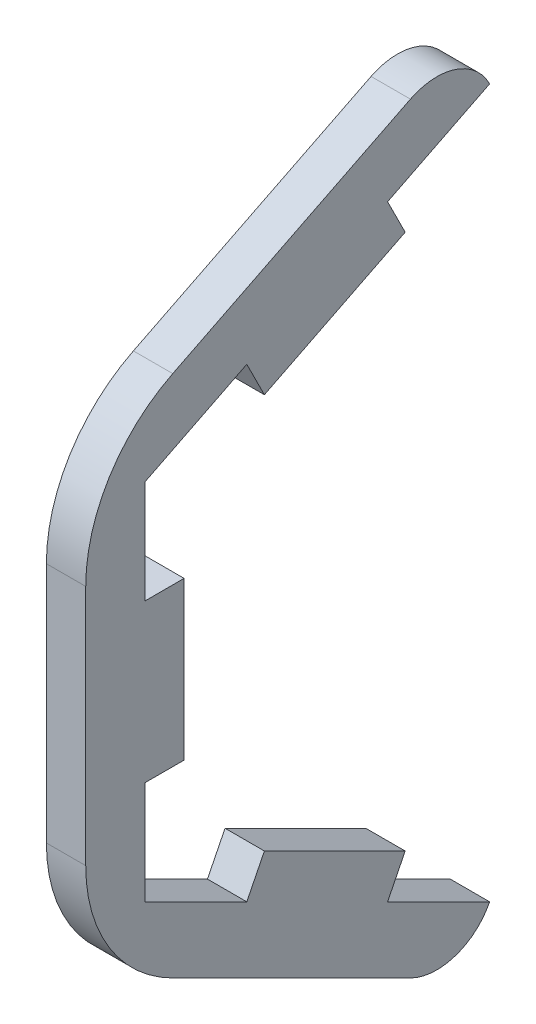
SolidWorks part; units mm, degrees
material "Plain Carbon Steel"
ref_plane "Front Plane" through (0, 0, 0) normal (0, 0, 1) x (1, 0, 0)
ref_plane "Top Plane" through (0, 0, 0) normal (0, 1, 0) x (1, 0, 0)
ref_plane "Right Plane" through (0, 0, 0) normal (1, 0, 0) x (0, 0, -1)
sketch "Sketch1" plane through (0, 0, 0) normal (1, 0, 0) x (0, 0, -1)
  line L0 (-160.655, 50.8) -> (93.345, 50.8)
  line L1 (93.345, 50.8) -> (93.345, -50.8)
  line L2 (93.345, -50.8) -> (-160.655, -50.8)
  line L3 (93.345, 0) -> (55.245, 50.8)
  line L4 (93.345, 0) -> (55.245, -50.8)
  circle A0 centre (0, 0) radius 38.1
  circle A1 centre (0, 0) radius 7.9375
  circle A2 centre (-38.1, 0) radius 7.9375
  circle A3 centre (-88.9, 0) radius 7.9375
  circle A4 centre (-88.9, 0) radius 39.751
  circle A5 centre (-38.1, 0) radius 25.4
  circle A6 centre (-160.655, 0) radius 11.1125
  circle A7 centre (-88.9, 0) radius 23.368
  circle A8 centre (-160.655, 0) radius 33.655
  circle A9 centre (-160.655, 0) radius 76.2
  circle A10 centre (-160.655, 0) radius 50.8
  dimension "D1" = 38.1
  dimension "D3" = 71.755
  dimension "D4" = 15.875
  dimension "D5" = 101.6
  dimension "D9" = 50.8
  dimension "D10" = 67.31
  dimension "D11" = 79.502
  dimension "D12" = 46.736
  dimension "D2" = 50.8
  dimension "D6" = 254
  dimension "D7" = 38.1
  dimension "D8" = 38.1
extrude "Boss-Extrude1" add sketch "Sketch1" along normal blind 12.7 contours A5 A0 A1 | A0 A5 | A10 A7 A9 A3 | A10 A7 A9 A4 | A7 A10 A4 | A7 A10 | A10 A4 A9 A7 | A9 A4 A5 A7 | A10 L2 A9 A4 | A4 A10 A8 | A8 A6 | A10 A4 A9 L0 | A9 A4 A5 A0 L2 L4 L3 L0 | A9 A3 A7 | A4 A5 | A0 A5 A4 A2 | A4 A8
hole_wizard "#8 Clearance Hole1" positions "Sketch3" profile "Sketch4" hole size "#8" standard "ANSI Inch" end condition through all
sketch "Sketch3" plane through (0, 0, 0) normal (-1, 0, 0) x (0, 0, 1)
  point P0 (-17.6911, 17.6911)
  point P3 (17.6911, 17.6911)
  point P6 (17.6911, -17.6911)
  point P9 (-17.6911, -17.6911)
sketch "Sketch4" plane through (0, 17.6911, -17.6911) normal (0, 1, 0) x (0, 0, 1)
  line L0 (0, 0) -> (0, 12.7)
  line L1 (0, 12.7) -> (2.2479, 12.7)
  line L2 (2.2479, 12.7) -> (2.2479, 0)
  line L5 (2.2479, 0) -> (0, 0)
  line L11 (0, -6.35) -> (0, 107.95) construction
  dimension "Thru Hole Dia." = 4.4958
  dimension "Thru Hole Depth" = 12.7
sketch "Sketch5" plane through (0, 0, 0) normal (-1, 0, 0) x (0, 0, 1)
  circle A0 centre (0, 0) radius 18.415
extrude "Cut-Extrude1" cut sketch "Sketch5" against normal through all
sketch "Sketch7" plane through (0, 0, 0) normal (-1, 0, 0) x (0, 0, 1)
  circle A0 centre (-55.245, 0) radius 9.525
  dimension "D1" = 38.1
extrude "Cut-Extrude2" cut sketch "Sketch7" against normal through all
sketch "Sketch8" plane through (12.7, 0, 0) normal (1, 0, 0) x (0, 0, -1)
  line L0 (-160.655, 50.8) -> (-211.455, 25.4)
  line L1 (-211.455, 25.4) -> (-211.455, -25.4)
  line L2 (-211.455, -25.4) -> (-160.655, -50.8)
  line L3 (-160.655, -50.8) -> (-233.2397, -50.8)
  line L4 (-233.2397, -50.8) -> (-233.2397, 50.8)
  line L5 (-233.2397, 50.8) -> (-160.655, 50.8)
  line L6 (-211.455, 0) -> (-160.655, 0) construction
  arc A0 (-160.655, 50.8) -> (-160.655, -50.8) centre (-160.655, 0) ccw construction
  dimension "D1" = 50.8
extrude "Cut-Extrude3" cut sketch "Sketch8" against normal through all
sketch "Sketch9" plane through (12.7, 0, 0) normal (1, 0, 0) x (0, 0, -1)
  line L0 (-160.655, 50.8) -> (-211.455, 25.4)
  line L1 (-211.455, 25.4) -> (-211.455, 0)
  line L2 (-211.455, 0) -> (-211.455, -25.4)
  line L3 (-211.455, -25.4) -> (-160.655, -50.8)
  line L4 (-160.655, -50.8) -> (-160.655, -40.64)
  line L5 (-160.655, -40.64) -> (-202.7493, 0)
  line L6 (-202.7493, 0) -> (-160.655, 40.64)
  line L7 (-160.655, 40.64) -> (-160.655, 50.8)
  line L8 (-160.655, -50.8) -> (-201.295, -30.48) construction
  line L9 (-201.295, 30.48) -> (-160.655, 50.8) construction
  arc A0 (-201.295, 30.48) -> (-201.295, -30.48) centre (-160.655, 0) ccw construction
extrude "Boss-Extrude2" add sketch "Sketch9" against normal blind 12.7
sketch "Sketch10" plane through (0, 0, 0) normal (-1, 0, 0) x (0, 0, 1)
  line L0 (-79.0575, -19.05) -> (-79.0575, 19.05)
  line L1 (-93.345, 0) -> (-55.245, -50.8) construction
  line L3 (-93.345, 0) -> (-55.245, 50.8) construction
  line L4 (-79.0575, 19.05) -> (-93.345, 0)
  line L5 (-93.345, 0) -> (-79.0575, -19.05)
extrude "Cut-Extrude4" cut sketch "Sketch10" against normal through all
sketch "Sketch11" plane through (0, 50.8, 0) normal (0, 1, 0) x (1, 0, 0)
  line L0 (0, -160.655) -> (0, 55.245) construction
  line L1 (0, 36.322) -> (12.7, 36.322)
  line L2 (0, 36.322) -> (0, -141.732)
  line L3 (0, -141.732) -> (12.7, -141.732)
  line L4 (12.7, 36.322) -> (12.7, -141.732)
  line L5 (12.7, -160.655) -> (12.7, 55.245) construction
  line L6 (12.7, -141.605) -> (0, -141.605) construction
  line L7 (0, 36.195) -> (12.7, 36.195) construction
  dimension "D1" = 0.127
  dimension "D2" = 0.127
extrude "Cut-Extrude5" cut sketch "Sketch11" against normal blind 3.175
mirror "Mirror1" about plane through (0, 0, 0) normal (0, 1, 0) of "Cut-Extrude5"
sketch "Sketch12" plane through (12.7, 0, 0) normal (1, 0, 0) x (0, 0, -1)
  line L16 (-162.154, 57.15) -> (-166.9165, 66.675)
  line L17 (-166.9165, 66.675) -> (-185.9665, 66.675)
  line L18 (-185.9665, 66.675) -> (-243.205, 43.9892)
  line L19 (-243.205, 43.9892) -> (-243.205, -43.9892)
  line L20 (-243.205, -43.9892) -> (-185.9665, -66.675)
  line L21 (-185.9665, -66.675) -> (-166.9165, -66.675)
  line L22 (-166.9165, -66.675) -> (-162.154, -57.15)
  line L23 (-243.205, 43.9892) -> (-217.805, 29.3245) construction
  line L24 (-217.805, -29.3245) -> (-243.205, -43.9892) construction
  line L32 (-162.154, -57.15) -> (-135.382, -57.15)
  line L33 (-135.382, -57.15) -> (-135.382, -53.975)
  line L34 (-135.382, -53.975) -> (29.972, -53.975)
  line L35 (29.972, -53.975) -> (29.972, -57.15)
  line L36 (29.972, -57.15) -> (58.42, -57.15)
  line L37 (58.42, -57.15) -> (85.4075, -21.1667)
  line L38 (85.4075, -21.1667) -> (85.4075, 21.1667)
  line L39 (85.4075, 21.1667) -> (58.42, 57.15)
  line L40 (58.42, 57.15) -> (29.972, 57.15)
  line L41 (29.972, 57.15) -> (29.972, 53.975)
  line L42 (29.972, 53.975) -> (-135.382, 53.975)
  line L43 (-135.382, 53.975) -> (-135.382, 57.15)
  line L44 (-135.382, 57.15) -> (-162.154, 57.15)
  line L45 (-162.154, 57.15) -> (-217.805, 29.3245)
  line L46 (-217.805, 29.3245) -> (-217.805, -29.3245)
  line L47 (-217.805, -29.3245) -> (-162.154, -57.15)
  line L48 (-162.154, -57.15) -> (-135.382, -57.15)
  line L49 (-135.382, -57.15) -> (-135.382, -53.975)
  line L50 (-135.382, -53.975) -> (29.972, -53.975)
  line L51 (29.972, -53.975) -> (29.972, -57.15)
  line L52 (29.972, -57.15) -> (58.42, -57.15)
  line L53 (58.42, -57.15) -> (85.4075, -21.1667)
  line L54 (85.4075, -21.1667) -> (85.4075, 21.1667)
  line L55 (85.4075, 21.1667) -> (58.42, 57.15)
  line L56 (58.42, 57.15) -> (29.972, 57.15)
  line L57 (29.972, 57.15) -> (29.972, 53.975)
  line L58 (29.972, 53.975) -> (-135.382, 53.975)
  line L59 (-135.382, 53.975) -> (-135.382, 57.15)
  line L60 (-135.382, 57.15) -> (-162.154, 57.15)
  line L61 (-162.154, 57.15) -> (-217.805, 29.3245)
  line L62 (-217.805, 29.3245) -> (-217.805, -29.3245)
  line L63 (-217.805, -29.3245) -> (-162.154, -57.15)
  circle A0 centre (-160.655, 0) radius 76.2
  dimension "D2" = 9.525
  dimension "D3" = 9.525
  dimension "D4" = 25.4
  dimension "D5" = 120
  dimension "D6" = 120
  dimension "D7" = 19.05
  dimension "D8" = 19.05
  dimension "D1" = 6.35
extrude "Boss-Extrude3" add sketch "Sketch12" against normal blind 6.35 separate body contours A0 L18 L19 L20 | L18 A0 L20 L21 L22 L63 L62 L61 L16 L17
sketch "Sketch13" plane through (12.7, 0, 0) normal (1, 0, 0) x (0, 0, -1)
  line L32 (-161.2546, -53.34) -> (-139.192, -53.34)
  line L33 (-139.192, -53.34) -> (-139.192, -50.165)
  line L34 (-139.192, -50.165) -> (33.782, -50.165)
  line L35 (33.782, -50.165) -> (33.782, -53.34)
  line L36 (33.782, -53.34) -> (56.515, -53.34)
  line L37 (56.515, -53.34) -> (81.5975, -19.8967)
  line L38 (81.5975, -19.8967) -> (81.5975, 19.8967)
  line L39 (81.5975, 19.8967) -> (56.515, 53.34)
  line L40 (56.515, 53.34) -> (33.782, 53.34)
  line L41 (33.782, 53.34) -> (33.782, 50.165)
  line L42 (33.782, 50.165) -> (-139.192, 50.165)
  line L43 (-139.192, 50.165) -> (-139.192, 53.34)
  line L44 (-139.192, 53.34) -> (-161.2546, 53.34)
  line L45 (-161.2546, 53.34) -> (-213.995, 26.9698)
  line L46 (-213.995, 26.9698) -> (-213.995, -26.9698)
  line L47 (-213.995, -26.9698) -> (-161.2546, -53.34)
  line L48 (-161.2546, -53.34) -> (-139.192, -53.34)
  line L49 (-139.192, -53.34) -> (-139.192, -50.165)
  line L50 (-139.192, -50.165) -> (33.782, -50.165)
  line L51 (33.782, -50.165) -> (33.782, -53.34)
  line L52 (33.782, -53.34) -> (56.515, -53.34)
  line L53 (56.515, -53.34) -> (81.5975, -19.8967)
  line L54 (81.5975, -19.8967) -> (81.5975, 19.8967)
  line L55 (81.5975, 19.8967) -> (56.515, 53.34)
  line L56 (56.515, 53.34) -> (33.782, 53.34)
  line L57 (33.782, 53.34) -> (33.782, 50.165)
  line L58 (33.782, 50.165) -> (-139.192, 50.165)
  line L59 (-139.192, 50.165) -> (-139.192, 53.34)
  line L60 (-139.192, 53.34) -> (-161.2546, 53.34)
  line L61 (-161.2546, 53.34) -> (-213.995, 26.9698)
  line L62 (-213.995, 26.9698) -> (-213.995, -26.9698)
  line L63 (-213.995, -26.9698) -> (-161.2546, -53.34)
  dimension "D1" = 2.54
extrude "Cut-Extrude6" cut sketch "Sketch13" against normal through all
hole_wizard "3/8 Clearance Hole1" [suppressed] positions "Sketch15" profile "Sketch14" hole size "3/8" standard "ANSI Inch"
sketch "Sketch15" plane through (12.7, 0, 0) normal (1, 0, 0) x (0, 0, -1)
  line L0 (-185.9665, -66.675) -> (-177.394, -49.53) construction
  line L1 (-217.805, -29.3245) -> (-162.154, -57.15) construction
  line L3 (-230.505, 49.0227) -> (-230.505, -49.0227) construction
  line L4 (-185.9665, 66.675) -> (-243.205, 43.9892) construction
  line L5 (-243.205, -43.9892) -> (-185.9665, -66.675) construction
  line L11 (-243.205, 0) -> (-230.505, 0) construction
  line L12 (-243.205, 43.9892) -> (-243.205, -43.9892) construction
  line L13 (-230.505, 0) -> (-217.805, 0) construction
  line L14 (-217.805, 29.3245) -> (-217.805, -29.3245) construction
  line L16 (-181.6803, -58.1025) -> (-230.505, -33.6901) construction
  line L18 (-185.9665, 66.675) -> (-177.394, 49.53) construction
  line L19 (-162.154, 57.15) -> (-217.805, 29.3245) construction
  line L23 (-230.505, 33.6901) -> (-181.6803, 58.1025) construction
  point P0 (-230.505, 0)
  point P2 (-230.505, 33.6901)
  point P4 (-202.1069, 47.8892)
  point P6 (-230.505, -33.6901)
  point P8 (-202.1069, -47.8892)
  dimension "D1" = 31.75
sketch "Sketch14" plane through (12.7, 0, 230.505) normal (0, 1, 0) x (0, 0, -1)
  line L0 (0, 0) -> (0, 15.7295)
  line L1 (0, 15.7295) -> (5.0419, 12.7)
  line L2 (5.0419, 12.7) -> (5.0419, 0)
  line L5 (5.0419, 0) -> (0, 0)
  line L10 (0, 15.7295) -> (-5.0419, 12.7) construction
  line L11 (0, -6.35) -> (0, 107.95) construction
  dimension "Hole Dia." = 10.0838
  dimension "Hole Depth" = 12.7
  dimension "Drill Angle" = 118
fillet "Fillet1" radius 12.7 6 edges at (9.525, 43.9892, 243.205) (9.525, -43.9892, 243.205) (9.525, -66.675, 166.9165) (9.525, -66.675, 185.9665) (9.525, 66.675, 166.9165) (9.525, 66.675, 185.9665)
sketch "Sketch16" plane through (12.7, 0, 0) normal (1, 0, 0) x (0, 0, -1)
  line L0 (-217.805, 29.3245) -> (-217.805, -29.3245) construction
  line L1 (-217.805, 12.7) -> (-211.455, 12.7)
  line L2 (-217.805, 12.7) -> (-217.805, -12.7)
  line L3 (-217.805, -12.7) -> (-211.455, -12.7)
  line L4 (-211.455, 12.7) -> (-211.455, -12.7)
  line L5 (-178.6203, -48.9169) -> (-175.7805, -43.2373)
  line L6 (-217.805, -29.3245) -> (-162.154, -57.15) construction
  line L7 (-175.7805, -43.2373) -> (-198.4989, -31.878)
  line L8 (-198.4989, -31.878) -> (-201.3387, -37.5576)
  line L9 (-201.3387, -37.5576) -> (-178.6203, -48.9169)
  line L10 (-201.3387, 37.5576) -> (-198.4989, 31.878)
  line L11 (-162.154, 57.15) -> (-217.805, 29.3245) construction
  line L12 (-198.4989, 31.878) -> (-175.7805, 43.2373)
  line L13 (-175.7805, 43.2373) -> (-178.6203, 48.9169)
  line L14 (-178.6203, 48.9169) -> (-201.3387, 37.5576)
  point P16 (-189.9795, 43.2373)
  point P19 (-189.9795, -43.2373)
  point P20 (-217.805, 0)
  dimension "D1" = 6.35
  dimension "D2" = 25.4
extrude "Boss-Extrude4" add sketch "Sketch16" against normal up to surface (6.35 mm away) up to face at (6.35, 0, 196.1429)
sketch "Sketch17" plane through (12.7, 0, 0) normal (1, 0, 0) x (0, 0, -1)
  line L22 (-174.7656, 66.675) -> (-183.5415, 66.675) construction
  line L23 (-188.2209, 65.7815) -> (-235.1844, 47.1681) construction
  line L24 (-243.205, 35.3616) -> (-243.205, -35.3616) construction
  line L25 (-235.1844, -47.1681) -> (-188.2209, -65.7815) construction
  line L26 (-183.5415, -66.675) -> (-174.7656, -66.675) construction
  line L27 (-174.7656, 66.675) -> (-183.5415, 66.675)
  line L28 (-188.2209, 65.7815) -> (-235.1844, 47.1681)
  line L29 (-243.205, 35.3616) -> (-243.205, -35.3616)
  line L30 (-235.1844, -47.1681) -> (-188.2209, -65.7815)
  line L31 (-183.5415, -66.675) -> (-174.7656, -66.675)
  line L32 (-197.079, 50.3368) -> (-168.1369, 64.8078)
  line L33 (-197.079, -50.3368) -> (-168.1369, -64.8078)
  line L34 (-227.33, 3.175) -> (-227.33, -3.175)
  line L44 (-184.7114, 56.9266) -> (-231.6748, 38.3132)
  line L45 (-233.68, 35.3616) -> (-233.68, -35.3616)
  line L46 (-231.6748, -38.3132) -> (-184.7114, -56.9266)
  line L47 (-183.5415, -57.15) -> (-183.4526, -57.15)
  line L48 (-183.4526, -57.15) -> (-191.3994, -53.1766)
  line L49 (-191.3994, -53.1766) -> (-188.5596, -47.497)
  line L50 (-188.5596, -47.497) -> (-194.2392, -44.6572)
  line L51 (-194.2392, -44.6572) -> (-197.079, -50.3368)
  line L52 (-197.079, -50.3368) -> (-227.33, -35.2113)
  line L53 (-227.33, -35.2113) -> (-227.33, -3.175)
  line L54 (-227.33, -3.175) -> (-220.98, -3.175)
  line L55 (-220.98, -3.175) -> (-220.98, 3.175)
  line L56 (-220.98, 3.175) -> (-227.33, 3.175)
  line L57 (-227.33, 3.175) -> (-227.33, 35.2113)
  line L58 (-227.33, 35.2113) -> (-197.079, 50.3368)
  line L59 (-197.079, 50.3368) -> (-194.2392, 44.6572)
  line L60 (-194.2392, 44.6572) -> (-188.5596, 47.497)
  line L61 (-188.5596, 47.497) -> (-191.3994, 53.1766)
  line L62 (-191.3994, 53.1766) -> (-183.4526, 57.15)
  line L63 (-183.4526, 57.15) -> (-183.5415, 57.15)
  line L72 (-197.079, -50.3368) -> (-227.33, -35.2113)
  line L73 (-227.33, -35.2113) -> (-227.33, -3.175)
  line L77 (-227.33, 3.175) -> (-227.33, 35.2113)
  line L78 (-227.33, 35.2113) -> (-197.079, 50.3368)
  arc A6 (-163.4063, 59.6546) -> (-174.7656, 66.675) centre (-174.7656, 53.975) ccw construction
  arc A7 (-183.5415, 66.675) -> (-188.2209, 65.7815) centre (-183.5415, 53.975) ccw construction
  arc A8 (-235.1844, 47.1681) -> (-243.205, 35.3616) centre (-230.505, 35.3616) ccw construction
  arc A9 (-243.205, -35.3616) -> (-235.1844, -47.1681) centre (-230.505, -35.3616) ccw construction
  arc A10 (-188.2209, -65.7815) -> (-183.5415, -66.675) centre (-183.5415, -53.975) ccw construction
  arc A11 (-174.7656, -66.675) -> (-163.4063, -59.6546) centre (-174.7656, -53.975) ccw construction
  arc A12 (-231.6748, 38.3132) -> (-233.68, 35.3616) centre (-230.505, 35.3616) ccw
  arc A13 (-233.68, -35.3616) -> (-231.6748, -38.3132) centre (-230.505, -35.3616) ccw
  arc A14 (-184.7114, -56.9266) -> (-183.5415, -57.15) centre (-183.5415, -53.975) ccw
  arc A15 (-183.5415, 57.15) -> (-184.7114, 56.9266) centre (-183.5415, 53.975) ccw
  arc A16 (-168.1369, 64.8078) -> (-174.7656, 66.675) centre (-174.7656, 53.975) ccw
  arc A17 (-183.5415, 66.675) -> (-188.2209, 65.7815) centre (-183.5415, 53.975) ccw
  arc A18 (-235.1844, 47.1681) -> (-243.205, 35.3616) centre (-230.505, 35.3616) ccw
  arc A19 (-243.205, -35.3616) -> (-235.1844, -47.1681) centre (-230.505, -35.3616) ccw
  arc A20 (-188.2209, -65.7815) -> (-183.5415, -66.675) centre (-183.5415, -53.975) ccw
  arc A21 (-174.7656, -66.675) -> (-168.1369, -64.8078) centre (-174.7656, -53.975) ccw
  dimension "D1" = 9.525
extrude "Cut-Extrude7" cut sketch "Sketch17" against normal through all
fillet "Fillet2" radius 9.525 2 edges at (9.525, -64.8078, 168.1369) (9.525, 64.8078, 168.1369)
fillet "Fillet3" radius 25.4 2 edges at (9.525, -35.2113, 227.33) (9.525, 35.2113, 227.33)
